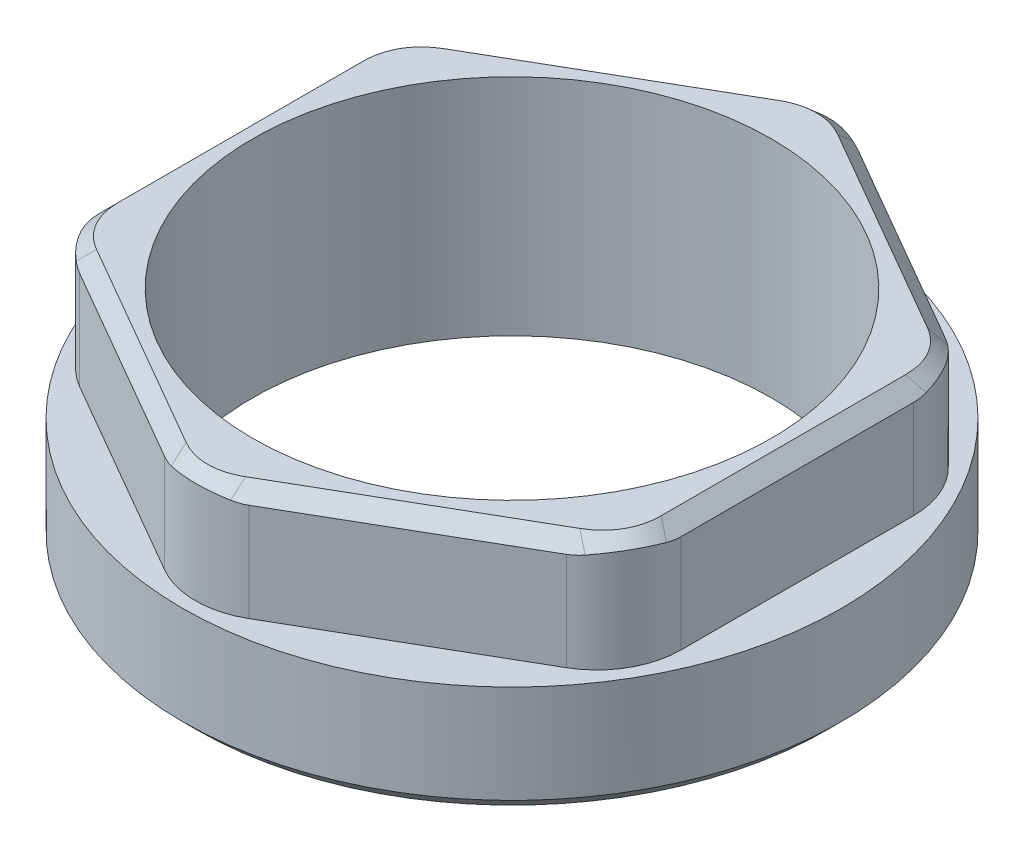
SolidWorks part; units mm, degrees
material "PVC 僵硬"
ref_plane "前视基准面" through (0, 0, 0) normal (0, 0, 1) x (1, 0, 0)
ref_plane "上视基准面" through (0, 0, 0) normal (0, 1, 0) x (1, 0, 0)
ref_plane "右视基准面" through (0, 0, 0) normal (1, 0, 0) x (0, 0, -1)
sketch "草图1" plane through (0, 0, 0) normal (0, 1, 0) x (1, 0, 0)
  circle A0 centre (0, 0) radius 11.75
  circle A1 centre (0, 0) radius 9.25
  dimension "D1" = 23.5
  dimension "D2" = 18.5
extrude "凸台-拉伸1" add sketch "草图1" along normal blind 4
sketch "草图2" plane through (0, 4, 0) normal (0, 1, 0) x (1, 0, 0)
  line L0 (0, 11.75) -> (0, -11.75) construction
  line L1 (0, 0) -> (10.1758, 5.875) construction
  line L2 (0, 0) -> (10.1758, -5.875) construction
  line L3 (0, 0) -> (-10.1758, -5.875) construction
  line L4 (0, 0) -> (-10.1758, 5.875) construction
  line L5 (0, 11.75) -> (-10.1758, 5.875)
  line L6 (-10.1758, 5.875) -> (-10.1758, -5.875)
  line L7 (-10.1758, -5.875) -> (0, -11.75)
  line L8 (0, -11.75) -> (10.1758, -5.875)
  line L9 (10.1758, -5.875) -> (10.1758, 5.875)
  line L10 (10.1758, 5.875) -> (0, 11.75)
  circle A0 centre (0, 0) radius 9.25
  circle A1 centre (0, 0) radius 11.75 construction
  dimension "D1" = 60
  dimension "D2" = 60
extrude "凸台-拉伸2" add sketch "草图2" along normal blind 4
chamfer "倒角1" distance 0.5 angle 45 7 edges at (-10.1758, 8, 0) (-5.0879, 8, -8.8125) (5.0879, 8, -8.8125) (10.1758, 8, 0) (5.0879, 8, 8.8125) (-5.0879, 8, 8.8125) (0, 0, 11.75)
fillet "圆角1" radius 3 12 edges at (10.1758, 5.75, -5.875) (9.9258, 7.75, -5.7307) (0, 7.75, 11.4613) (0, 5.75, 11.75) (-10.1758, 5.75, 5.875) (-9.9258, 7.75, 5.7307) (-10.1758, 5.75, -5.875) (-9.9258, 7.75, -5.7307) (0, 5.75, -11.75) (0, 7.75, -11.4613) (10.1758, 5.75, 5.875) (9.9258, 7.75, 5.7307)
